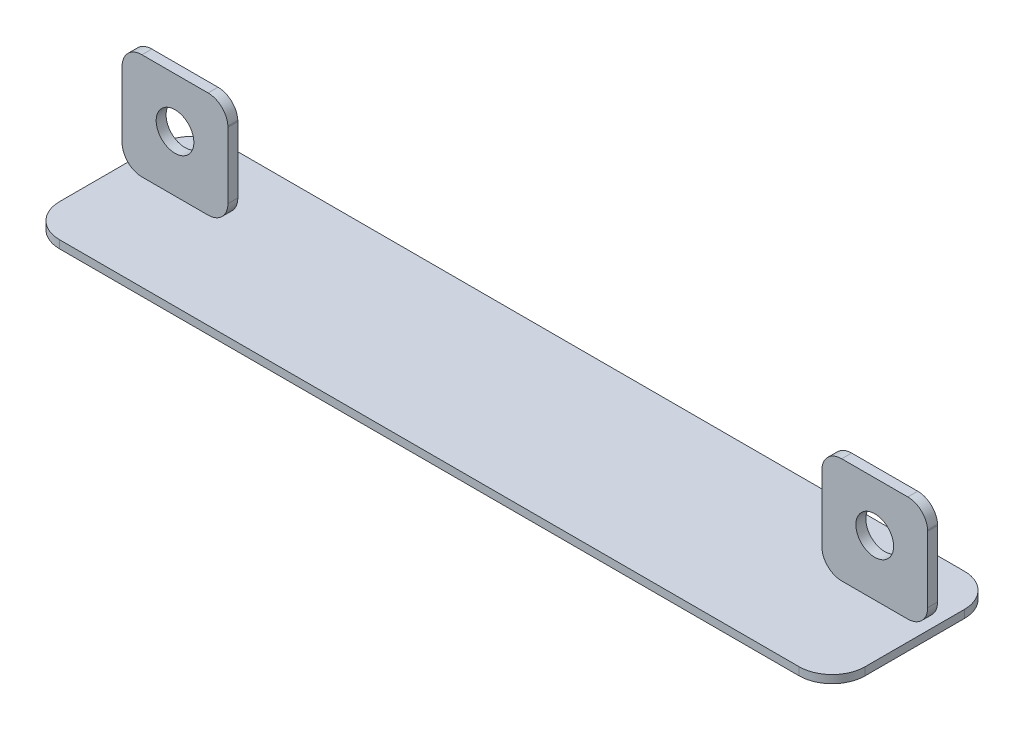
SolidWorks part; units mm, degrees
ref_plane "Front Plane" through (0, 0, 0) normal (0, 0, 1) x (1, 0, 0)
ref_plane "Top Plane" through (0, 0, 0) normal (0, 1, 0) x (1, 0, 0)
ref_plane "Right Plane" through (0, 0, 0) normal (1, 0, 0) x (0, 0, -1)
sketch "Sketch3" plane through (0, 0, 0) normal (0, 0, 1) x (1, 0, 0)
  line L6 (-7.9975, -43.2281) -> (-8, -43.4)
  line L7 (-8, -43.4) -> (-8, -53.4)
  line L8 (-5, -56.4) -> (5, -56.4)
  line L9 (8, -53.4) -> (8, -43.4)
  line L10 (8, -43.4) -> (7.9975, -43.2281)
  line L11 (5, -40.4) -> (-5, -40.4)
  line L12 (-7.9975, -43.2281) -> (-8, -43.4)
  line L13 (-8, -43.4) -> (-8, -53.4)
  line L14 (-5, -56.4) -> (5, -56.4)
  line L15 (8, -53.4) -> (8, -43.4)
  line L16 (8, -43.4) -> (7.9975, -43.2281)
  line L17 (5, -40.4) -> (-5, -40.4)
  line L18 (110.8, -40.4) -> (100.8, -40.4)
  line L19 (97.8025, -43.2281) -> (97.8, -43.4)
  line L20 (97.8, -43.4) -> (97.8, -53.4)
  line L21 (100.8, -56.4) -> (110.8, -56.4)
  line L22 (113.8, -53.4) -> (113.8, -43.4)
  line L23 (113.8, -43.4) -> (113.7975, -43.2281)
  line L24 (110.8, -40.4) -> (100.8, -40.4)
  line L25 (97.8025, -43.2281) -> (97.8, -43.4)
  line L26 (97.8, -43.4) -> (97.8, -53.4)
  line L27 (100.8, -56.4) -> (110.8, -56.4)
  line L28 (113.8, -53.4) -> (113.8, -43.4)
  line L29 (113.8, -43.4) -> (113.7975, -43.2281)
  circle A0 centre (0, -47.9524) radius 2.85 construction
  circle A1 centre (0, -47.9524) radius 2.85
  arc A2 (-5, -40.4) -> (-7.9975, -43.2281) centre (-5.0013, -43.4012) ccw
  arc A3 (-8, -53.4) -> (-5, -56.4) centre (-5, -53.4) ccw
  arc A4 (5, -56.4) -> (8, -53.4) centre (5, -53.4) ccw
  arc A5 (7.9975, -43.2281) -> (5, -40.4) centre (5.0013, -43.4012) ccw
  arc A6 (-5, -40.4) -> (-7.9975, -43.2281) centre (-5.0013, -43.4012) ccw
  arc A7 (-8, -53.4) -> (-5, -56.4) centre (-5, -53.4) ccw
  arc A8 (5, -56.4) -> (8, -53.4) centre (5, -53.4) ccw
  arc A9 (7.9975, -43.2281) -> (5, -40.4) centre (5.0013, -43.4012) ccw
  circle A10 centre (105.8, -47.9524) radius 2.85 construction
  circle A11 centre (105.8, -47.9524) radius 2.85
  arc A12 (100.8, -40.4) -> (97.8025, -43.2281) centre (100.7987, -43.4012) ccw
  arc A13 (97.8, -53.4) -> (100.8, -56.4) centre (100.8, -53.4) ccw
  arc A14 (110.8, -56.4) -> (113.8, -53.4) centre (110.8, -53.4) ccw
  arc A15 (113.7975, -43.2281) -> (110.8, -40.4) centre (110.8013, -43.4012) ccw
  arc A16 (100.8, -40.4) -> (97.8025, -43.2281) centre (100.7987, -43.4012) ccw
  arc A17 (97.8, -53.4) -> (100.8, -56.4) centre (100.8, -53.4) ccw
  arc A18 (110.8, -56.4) -> (113.8, -53.4) centre (110.8, -53.4) ccw
  arc A19 (113.7975, -43.2281) -> (110.8, -40.4) centre (110.8013, -43.4012) ccw
  dimension "D1" = 0
  dimension "D2" = 0
extrude "Boss-Extrude3" add sketch "Sketch3" along normal up to surface (1.5 mm away)
sketch "Sketch2" plane through (0, -56.4, 0) normal (0, -1, 0) x (1, 0, 0)
  line L0 (-8, -78.8637) -> (-8, 0) construction
  line L1 (-8, -9.0521) -> (113.8, -9.0521)
  line L2 (-8, -9.0521) -> (-8, 15.9479)
  line L3 (-8, 15.9479) -> (113.8, 15.9479)
  line L4 (113.8, -9.0521) -> (113.8, 15.9479)
  line L5 (113.8, 0) -> (113.8, -78.8637) construction
  line L6 (-5, 15.9479) -> (5, 15.9479) construction
  point P4 (0, 0)
  point P5 (0, 0)
  point P8 (0, 0)
  point P11 (0, 0)
  dimension "D1" = 25
extrude "Boss-Extrude2" add sketch "Sketch2" along normal blind 1.2
fillet "Fillet1" radius 5 4 edges at (113.8, -57, 15.9479) (113.8, -57, -9.0521) (-8, -57, -9.0521) (-8, -57, 15.9479)
